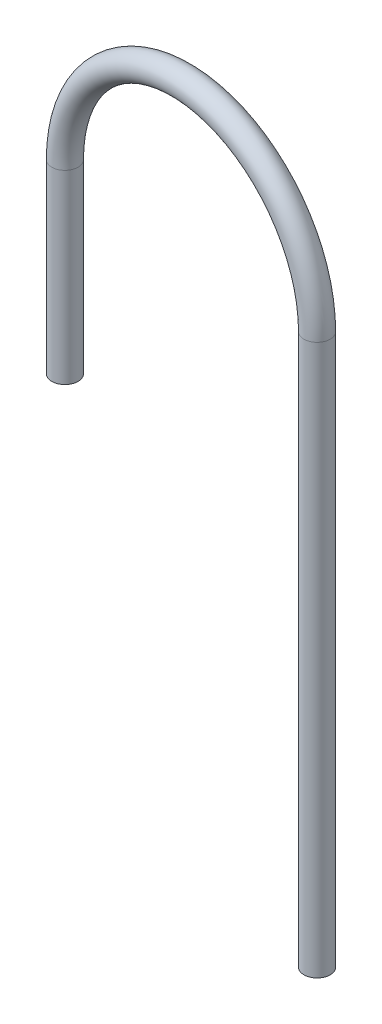
SolidWorks part; units mm, degrees
material "PE faible/moyenne densité"
ref_plane "Front" through (0, 0, 0) normal (0, 0, 1) x (1, 0, 0)
ref_plane "Top" through (0, 0, 0) normal (0, 1, 0) x (1, 0, 0)
ref_plane "Right" through (0, 0, 0) normal (1, 0, 0) x (0, 0, -1)
sketch3d "Esquisse3D1"
  line L0 (14, 165, -59.25) -> (14, 207.375, -59.25)
  line L1 (76.8149, 207.375, -54.0281) -> (76.8149, 81.65, -54.0281)
  arc A0 (14, 207.375, -59.25) -> (76.8149, 207.375, -54.0281) centre (45.4075, 207.375, -56.6391) ccw
  circle A1 centre (76.8149, 89.65, -54.0281) radius 1.1 construction
  point P3 (48.0184, 207.375, -88.0465)
  point P9 (76.8149, 88.55, -54.0281)
  dimension "D4" = 125.725
  dimension "D1" = 165
  dimension "D2" = 14
  dimension "D3" = 59.25
  dimension "D5" = 81.65
sweep "Balayage-Mince1" add path "Esquisse3D1" circular profile diameter 6 parameters "D1"=1, "D3"=6
equation "\"D4@Esquisse3D1\"=140-((\"D5@Esquisse3D1\"-81)/2)"
